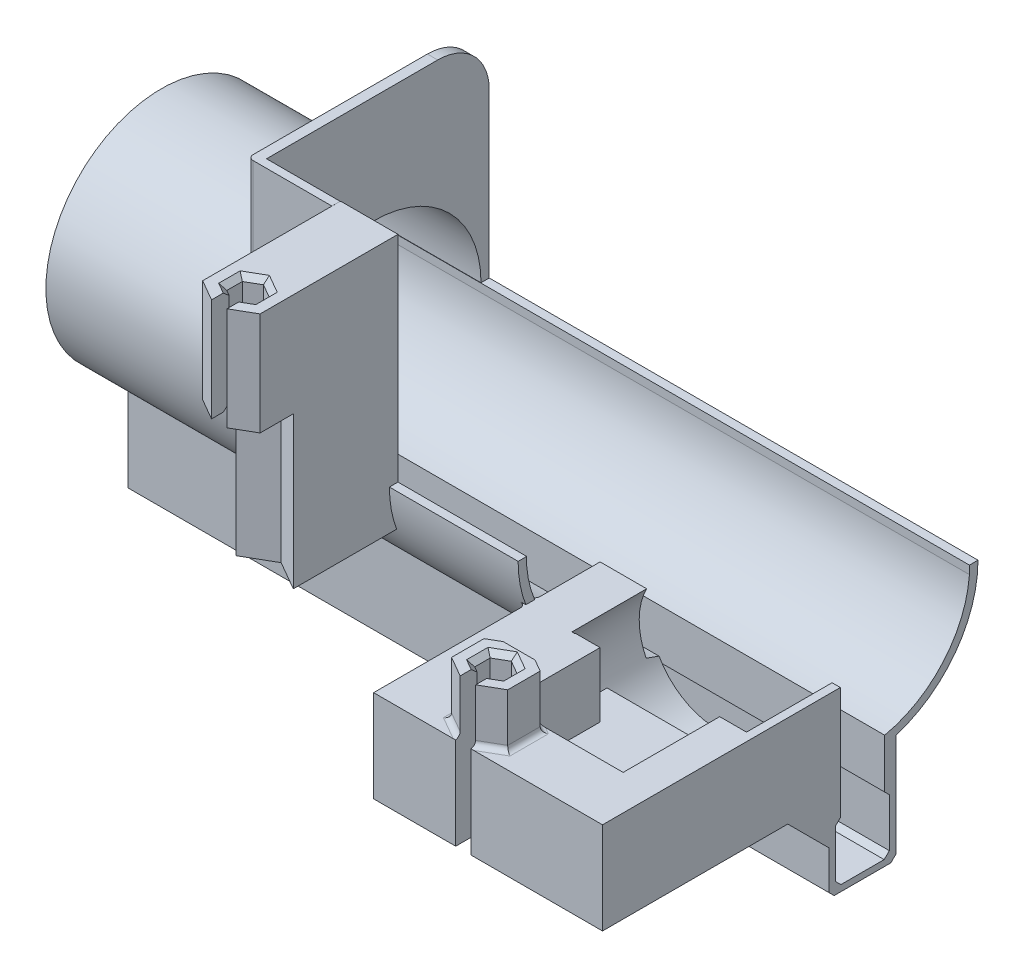
SolidWorks part; units mm, degrees
note: The reader was unsure of these and kept them because the rebuilt part matched: shared geometry of "Sketch6<5>", "Sketch6<6>", "Sketch16<2>", "Sketch18<2>", "Sketch17<3>", "Sketch21<2>", "Sketch18<3>".
ref_plane "Front Plane" through (0, 0, 0) normal (0, 0, 1) x (1, 0, 0)
ref_plane "Top Plane" through (0, 0, 0) normal (0, 1, 0) x (1, 0, 0)
ref_plane "Right Plane" through (0, 0, 0) normal (1, 0, 0) x (0, 0, -1)
sketch "Sketch1" plane through (0, 0, 0) normal (0, 1, 0) x (1, 0, 0)
  line L1 (0, 0) -> (136, 0)
  line L2 (0, 0) -> (0, 13)
  line L3 (0, 13) -> (136, 13)
  line L4 (136, 0) -> (136, 13)
  dimension "D1" = 13
  dimension "D2" = 136
extrude "Boss-Extrude1" add sketch "Sketch1" along normal blind 21
sketch "Sketch4" plane through (136, 0, 0) normal (1, 0, 0) x (0, 0, -1)
  line L0 (1.3, 2.2) -> (2.3, 1.2)
  line L1 (2.3, 12.6) -> (10.7, 12.6)
  line L2 (1.3, 11.6) -> (1.3, 2.2)
  line L3 (2.3, 1.2) -> (10.7, 1.2)
  line L4 (11.7, 11.6) -> (11.7, 2.2)
  line L5 (0, 21) -> (0, 0) construction
  line L6 (0, 0) -> (13, 0) construction
  line L7 (1.3, 2.2) -> (2.3, 1.2)
  line L8 (10.7, 1.2) -> (11.7, 2.2)
  line L10 (1.3, 11.6) -> (2.3, 12.6)
  line L11 (10.7, 12.6) -> (11.7, 11.6)
  dimension "D2" = 1.3
  dimension "D3" = 1.2
  dimension "D4" = 1
  dimension "D5" = 45
  dimension "D6" = 45
  dimension "D7" = 1
  dimension "D8" = 11.4
  dimension "D9" = 45
  dimension "D10" = 45
  dimension "D11" = 1
  dimension "D12" = 1
  dimension "D13" = 8.4
extrude "Cut-Extrude1" cut sketch "Sketch4" against normal blind 135 contours L3 L8 L4 L1 L2 L0
chamfer "Chamfer1" distance 1 angle 45 1 edges at (68, 0, 0)
chamfer "Chamfer2" distance 1 angle 45 1 edges at (68, 0, -13)
sketch "Sketch6" plane through (0, 21, 0) normal (0, 1, 0) x (1, 0, 0)
  line L0 (136, 0) -> (136, 13) construction
  line L1 (1, 10.8) -> (136, 10.8)
  line L2 (1, 10.8) -> (1, 2.2)
  line L3 (1, 2.2) -> (136, 2.2)
  line L4 (136, 10.8) -> (136, 2.2)
  point P4 (136, 6.5)
  dimension "D1" = 135
  dimension "D2" = 8.6
extrude "Cut-Extrude3" cut sketch "Sketch6" against normal blind 9
sketch "Sketch8" plane through (0, 0, 0) normal (-1, 0, 0) x (0, 0, 1)
  line L0 (-13, 21) -> (-13, 1) construction
  line L1 (-10.5, 20) -> (-2.5, 20)
  line L2 (-10.5, 20) -> (-10.5, 12.46)
  line L3 (-10.5, 12.46) -> (-2.5, 12.46)
  line L4 (-2.5, 20) -> (-2.5, 12.46)
  line L5 (-13, 21) -> (0, 21) construction
  line L6 (0, 21) -> (0, 1) construction
  line L8 (-9, 20) -> (-4, 20)
  line L9 (-9, 20) -> (-9, 12.46)
  line L10 (-9, 12.46) -> (-4, 12.46)
  line L11 (-4, 20) -> (-4, 12.46)
  point P14 (-6.5, 20)
  point P15 (-6.5, 20)
  point P16 (-6.5, 12.46)
  point P17 (-6.5, 12.46)
  dimension "D1" = 2.5
  dimension "D2" = 1
  dimension "D3" = 7.54
  dimension "D4" = 2.5
  dimension "D5" = 5
extrude "Cut-Extrude5" cut sketch "Sketch8" against normal blind 1 contours L9 L1 L2 L3 | L1 L11 L3 L4
sketch "Sketch9" plane through (0, 0, 0) normal (-1, 0, 0) x (0, 0, 1)
  line L1 (-13, 20) -> (0, 20) construction
  line L2 (-28.9, 42.4) -> (-27.2384, 42.4)
  line L4 (-27.2384, 42.4) -> (-27.2384, 40.8)
  line L5 (14.2384, 40.8) -> (14.2384, 42.4)
  line L6 (14.2384, 42.4) -> (15.9, 42.4)
  line L7 (-28.9, 42.4) -> (15.9, 42.4) construction
  line L8 (-27.2384, 40.8) -> (14.2384, 40.8) construction
  line L9 (-10.5, 20) -> (-9, 20) construction
  line L12 (-13, 21) -> (-13, 1) construction
  line L13 (0, 21) -> (0, 1) construction
  arc A0 (-28.9, 42.4) -> (15.9, 42.4) centre (-6.5, 42.4) ccw
  arc A1 (-27.2384, 40.8) -> (14.2384, 40.8) centre (-6.5, 42.4) ccw
  point P4 (-6.5, 20)
  dimension "D1" = 44.8
  dimension "D2" = 1.6
extrude "Boss-Extrude3" add sketch "Sketch9" against normal blind 136 separate body
sketch "Sketch11" plane through (0, 0, 0) normal (-1, 0, 0) x (0, 0, 1)
  circle A0 centre (-6.5, 42.4) radius 22.4
  circle A1 centre (-6.5, 42.4) radius 20.8
  dimension "D1" = 44.8
  dimension "D2" = 41.6
extrude "Boss-Extrude6" add sketch "Sketch11" against normal blind 41.2
extrude "Cut-Extrude11" cut sketch "Sketch6<5>" along normal blind 35
sketch "Sketch6<5>" plane through (0, 21, 0) normal (0, 1, 0) x (1, 0, 0) same geometry as "Sketch6"
extrude "Cut-Extrude12" cut sketch "Sketch6<6>" against normal blind 1
sketch "Sketch6<6>" plane through (0, 21, 0) normal (0, 1, 0) x (1, 0, 0) same geometry as "Sketch6"
sketch "Sketch13" plane through (0, 0, 0) normal (0, 0, 1) x (1, 0, 0)
  line L1 (136, 20.9638) -> (89, 20.9638)
  line L2 (136, 20.9638) -> (136, 42.9638)
  line L3 (136, 42.9638) -> (89, 42.9638)
  line L4 (89, 20.9638) -> (89, 42.9638)
  dimension "D1" = 47
  dimension "D2" = 22
extrude "Cut-Extrude13" cut sketch "Sketch13" along normal blind 32
ref_plane "Plane1" through (136, 22.0493, -2.2) normal (1, 0, 0) x (0, 0, -1)
ref_plane "Plane2" through (0, 22.7, 0) normal (0, 1, 0) x (1, 0, 0)
sketch "Sketch16" plane through (0, 22.7, 0) normal (0, 1, 0) x (1, 0, 0)
  line L0 (136, 0) -> (89, 0) construction
  line L1 (109.0218, -40.64) -> (111.6198, -39.14)
  line L2 (111.6198, -39.14) -> (111.6198, -36.14)
  line L3 (111.6198, -36.14) -> (109.0218, -34.64)
  line L4 (109.0218, -34.64) -> (106.4237, -36.14)
  line L5 (106.4237, -36.14) -> (106.4237, -39.14)
  line L6 (106.4237, -39.14) -> (109.0218, -40.64)
  line L8 (109.0218, -31.35) -> (103.5745, -34.495)
  line L9 (103.5745, -34.495) -> (103.5745, -40.785)
  line L10 (103.5745, -40.785) -> (109.0218, -43.93)
  line L11 (109.0218, -43.93) -> (114.4691, -40.785)
  line L12 (114.4691, -40.785) -> (114.4691, -34.495)
  line L13 (114.4691, -34.495) -> (109.0218, -31.35)
  circle A0 centre (109.0218, -37.64) radius 2.5981 construction
  circle A1 centre (109.0218, -37.64) radius 5.4473 construction
  dimension "D1" = 6
  dimension "D2" = 34.64
  dimension "D3" = 40.01
  dimension "D4" = 12.58
extrude "Boss-Extrude7" add sketch "Sketch16" along normal blind 22 separate body
extrude "Boss-Extrude8" add sketch "Sketch16<2>" against normal blind 4.79
sketch "Sketch16<2>" plane through (0, 22.7, 0) normal (0, 1, 0) x (1, 0, 0) same geometry as "Sketch16"
sketch "Sketch17" plane through (0, 17.91, 0) normal (0, -1, 0) x (1, 0, 0)
  line L1 (94.0218, 43.93) -> (136, 43.93)
  line L3 (94.0218, 0) -> (136, 0)
  line L4 (136, 43.93) -> (136, 0)
  line L5 (0, 0) -> (136, 0) construction
  line L6 (94.0218, 0) -> (91.6018, 0)
  line L7 (91.6018, 0) -> (91.6018, 43.93)
  line L8 (91.6018, 43.93) -> (94.0218, 43.93)
  dimension "D1" = 2.42
  dimension "D2" = 15
extrude "Boss-Extrude10" add sketch "Sketch17" against normal blind 16.45
sketch "Sketch18" plane through (0, 0, 0) normal (0, 0, 1) x (1, 0, 0)
  circle A0 centre (112.185, 28.4) radius 13
  circle A1 centre (112.185, 28.4) radius 9.75 construction
  dimension "D1" = 26
extrude "Cut-Extrude14" cut sketch "Sketch18" against normal blind 8
extrude "Cut-Extrude15" cut sketch "Sketch18<2>" along normal blind 8
sketch "Sketch18<2>" plane through (0, 0, 0) normal (0, 0, 1) x (1, 0, 0) same geometry as "Sketch18"
sketch "Sketch21" plane through (0, 34.36, 0) normal (0, 1, 0) x (1, 0, 0)
  line L0 (136, -43.93) -> (109.0218, -43.93) construction
  line L1 (106, -8) -> (129.2, -8)
  line L2 (106, -8) -> (106, -33.13)
  line L3 (106, -33.13) -> (129.2, -33.13)
  line L4 (129.2, -8) -> (129.2, -33.13)
  line L5 (136, 0) -> (136, -43.93) construction
  line L6 (123.7383, -8) -> (100.6317, -8) construction
  dimension "D1" = 10.8
  dimension "D2" = 6.8
  dimension "D3" = 23.2
extrude "Cut-Extrude16" cut sketch "Sketch21" against normal blind 12.5
extrude "Boss-Extrude11" add sketch "Sketch17<3>" along normal blind 1.39
sketch "Sketch17<3>" plane through (0, 17.91, 0) normal (0, -1, 0) x (1, 0, 0) same geometry as "Sketch17"
extrude "Cut-Extrude18" cut sketch "Sketch21<2>" along normal blind 33.8
sketch "Sketch21<2>" plane through (0, 34.36, 0) normal (0, 1, 0) x (1, 0, 0) same geometry as "Sketch21"
sketch "Sketch23" plane through (0, 34.36, 0) normal (0, 1, 0) x (1, 0, 0)
  line L1 (101.2, -8) -> (123.7383, -8)
  line L2 (101.2, -8) -> (101.2, -14.4)
  line L3 (101.2, -14.4) -> (134.4, -14.4)
  line L4 (134.4, -8) -> (134.4, -14.4)
  line L6 (129.2, -33.13) -> (129.2, -8) construction
  line L7 (104.5065, -8) -> (99.185, -8) construction
  line L10 (134.4, -8) -> (134.4, 0.5)
  line L11 (134.4, 0.5) -> (123.7383, 0.5)
  line L12 (123.7383, -8) -> (123.7383, 0.5)
  line L13 (129.2, -33.13) -> (129.2, -8) construction
  line L14 (123.7383, -8) -> (123.7383, 0) construction
  dimension "D1" = 33.2
  dimension "D2" = 5.2
  dimension "D3" = 6.4
  dimension "D4" = 14.9
extrude "Cut-Extrude20" cut sketch "Sketch23" against normal blind 12.5
sketch "Sketch24" plane through (0, 0, 14.4) normal (0, 0, -1) x (-1, 0, 0)
  line L1 (-134.4, 21.86) -> (-134.4, 34.36) construction
  line L2 (-101.2, 21.86) -> (-101.2, 34.36) construction
  line L3 (-101.2, 34.36) -> (-106, 34.36) construction
  line L4 (-129.2, 34.36) -> (-134.4, 34.36) construction
  circle A0 centre (-131.31, 28.41) radius 1.2
  circle A1 centre (-103.81, 28.41) radius 1.2
  dimension "D2" = 3.09
  dimension "D3" = 2.4
  dimension "D4" = 2.4
  dimension "D1" = 5.95
  dimension "D5" = 2.61
  dimension "D6" = 5.95
extrude "Cut-Extrude21" cut sketch "Sketch24" against normal blind 12
sketch "Sketch25" plane through (0, 16.52, 0) normal (0, -1, 0) x (1, 0, 0)
  line L1 (109.0218, 34.64) -> (111.6198, 36.14)
  line L2 (111.6198, 36.14) -> (111.6198, 39.14)
  line L3 (111.6198, 39.14) -> (109.0218, 40.64)
  line L4 (109.0218, 40.64) -> (106.4237, 39.14)
  line L5 (106.4237, 39.14) -> (106.4237, 36.14)
  line L6 (106.4237, 36.14) -> (109.0218, 34.64)
  circle A0 centre (109.0218, 37.64) radius 2.5981 construction
extrude "Cut-Extrude22" cut sketch "Sketch25" against normal blind 30
extrude "Cut-Extrude23" cut sketch "Sketch18<3>" along normal blind 8
sketch "Sketch18<3>" plane through (0, 0, 0) normal (0, 0, 1) x (1, 0, 0) same geometry as "Sketch18"
chamfer "Chamfer3" distance 8 angle 45 1 edges at (126.7319, 16.52, 0)
sketch "Sketch26" plane through (0, 21.86, 0) normal (0, 1, 0) x (1, 0, 0)
  line L1 (136, 0) -> (123.5282, 0)
  line L2 (136, 0) -> (136, 2.2)
  line L3 (136, 2.2) -> (123.5282, 2.2)
  line L4 (123.5282, 0) -> (123.5282, 2.2)
extrude "Cut-Extrude24" cut sketch "Sketch26" along normal blind 8
sketch "Sketch27" plane through (0, 0, 8) normal (0, 0, 1) x (1, 0, 0)
  line L0 (123.7383, 21.86) -> (123.7383, 22.44)
  line L1 (123.7383, 21.86) -> (123.7383, 22.44) construction
  line L2 (123.7383, 22.44) -> (123.4201, 21.86)
  line L3 (123.4201, 21.86) -> (123.7383, 21.86)
  arc A0 (123.4201, 21.86) -> (123.7383, 22.44) centre (112.185, 28.4) ccw construction
extrude "Cut-Extrude25" cut sketch "Sketch27" against normal blind 11
sketch "Sketch28" plane through (0, 21.86, 0) normal (0, 1, 0) x (1, 0, 0)
  line L0 (136, 2.2) -> (123.4201, 2.2) construction
  line L1 (136, 0) -> (134.4, 0)
  line L2 (136, 0) -> (136, 2.2)
  line L3 (136, 2.2) -> (134.4, 2.2)
  line L4 (134.4, 0) -> (134.4, 2.2)
  line L5 (134.4, -14.4) -> (134.4, 0) construction
extrude "Boss-Extrude14" add sketch "Sketch28" along normal blind 12.5
sketch "Sketch29" plane through (0, 0, 8) normal (0, 0, -1) x (-1, 0, 0)
  line L0 (-101.2, 21.86) -> (-101.2, 34.36)
  line L1 (-101.2, 34.36) -> (-100.6317, 34.36)
  line L2 (-109.0218, 34.36) -> (-91.6018, 34.36) construction
  line L3 (-100.6317, 34.36) -> (-101.2, 34.36) construction
  line L4 (-101.2, 21.86) -> (-100.5299, 22.6417)
  line L5 (-101.2, 21.86) -> (-100.9499, 21.86)
  arc A0 (-100.9499, 21.86) -> (-100.6317, 34.36) centre (-112.185, 28.4) ccw
  line M1 (-100.6317, 34.36) -> (-101.2, 34.36)
  line M2 (-101.2, 34.36) -> (-101.2, 21.86)
  arc M6 (-106.9062, 16.52) -> (-100.6317, 34.36) centre (-112.185, 28.4) ccw
  dimension "D1" = 26
extrude "Cut-Extrude26" cut sketch "Sketch29" against normal blind 6.5 contours L4 M2 M6 M1 | L4 L5 M6
fillet "Fillet2" radius 1 3 edges at (111.7454, 34.36, 42.3575) (113.2869, 34.36, 33.8125) (114.4691, 34.36, 37.64)
fillet "Fillet3" radius 1 3 edges at (104.7872, 34.36, 33.7948) (103.5745, 34.36, 37.64) (106.2981, 34.36, 42.3575)
sketch "Sketch30" plane through (89, 0, 0) normal (1, 0, 0) x (0, 0, -1)
  line L0 (-14.2384, 42.4) -> (-15.9, 42.4)
  line L1 (27.2384, 42.4) -> (28.9, 42.4)
  line L2 (2.2, 20.4166) -> (2.2, 22.0493)
  line L3 (2.2, 12.5) -> (2.2, 22.0493) construction
  arc A0 (-14.2384, 42.4) -> (27.2384, 42.4) centre (6.5, 42.4) ccw
  arc A1 (-15.9, 42.4) -> (28.9, 42.4) centre (6.5, 42.4) ccw
  dimension "D1" = 44.8
extrude "Boss-Extrude15" add sketch "Sketch30" along normal up to surface (2.6018 mm away) up to face at (91.6018, 22.1536, 15.9767)
fillet "Fillet5" radius 1 1 edges at (91.6018, 27.1225, 7.6151)
fillet "Fillet6" radius 1 1 edges at (91.6018, 25.9956, 8.753)
ref_plane "Plane3" through (0, 64.02, 0) normal (0, 1, 0) x (1, 0, 0)
sketch "Sketch31" plane through (0, 64.02, 0) normal (0, 1, 0) x (1, 0, 0)
  line L0 (91.6018, -15.9) -> (41.2, -15.9) construction
  line L1 (61.0618, -40.76) -> (63.6598, -39.26)
  line L2 (63.6598, -39.26) -> (63.6598, -36.26)
  line L3 (63.6598, -36.26) -> (61.0618, -34.76)
  line L4 (61.0618, -34.76) -> (58.4637, -36.26)
  line L5 (58.4637, -36.26) -> (58.4637, -39.26)
  line L6 (58.4637, -39.26) -> (61.0618, -40.76)
  line L7 (103.5745, -34.495) -> (103.5745, -40.785) construction
  line L9 (61.0618, -31.325) -> (55.4889, -34.5425)
  line L10 (55.4889, -34.5425) -> (55.4889, -40.9775)
  line L11 (55.4889, -40.9775) -> (61.0618, -44.195)
  line L12 (61.0618, -44.195) -> (66.6346, -40.9775)
  line L13 (66.6346, -40.9775) -> (66.6346, -34.5425)
  line L14 (66.6346, -34.5425) -> (61.0618, -31.325)
  line L15 (91.6018, -15.9) -> (91.6018, -14.2384) construction
  circle A0 centre (61.0618, -37.76) radius 2.5981 construction
  circle A1 centre (61.0618, -37.76) radius 5.5729 construction
  dimension "D1" = 6
  dimension "D2" = 12.87
  dimension "D3" = 18.86
  dimension "D4" = 30.54
extrude "Boss-Extrude16" add sketch "Sketch31" along normal blind 20 separate body
ref_plane "Plane5" through (0, 0, 14.2384) normal (0, 0, -1) x (-1, 0, 0)
sketch "Sketch32" plane through (0, 84.02, 0) normal (0, 1, 0) x (1, 0, 0)
  line L0 (55.4889, -34.5425) -> (55.4889, -14.2384)
  line L3 (66.6346, -34.5425) -> (66.6346, -14.2384)
  line L5 (66.6346, -14.2384) -> (55.4889, -14.2384)
  line L6 (55.4889, -34.5425) -> (61.0618, -31.325)
  line L7 (61.0618, -31.325) -> (66.6346, -34.5425)
  line L8 (91.6018, -14.2384) -> (0, -14.2384) construction
  line M1 (66.6346, -34.5425) -> (61.0618, -31.325)
  line M2 (61.0618, -31.325) -> (55.4889, -34.5425)
extrude "Boss-Extrude17" add sketch "Sketch32" against normal blind 49.4 contours L3 L5 L0 M2 M1
sketch "Sketch36" plane through (0, 0, 14.2384) normal (0, 0, -1) x (-1, 0, 0)
  line L1 (-66.6318, 42.4) -> (-55.4818, 42.4)
  line L2 (-66.6318, 42.4) -> (-66.6318, 34.62)
  line L3 (-66.6318, 34.62) -> (-55.4818, 34.62)
  line L4 (-55.4818, 42.4) -> (-55.4818, 34.62)
  line L5 (-91.6018, 40.8) -> (-91.6018, 34.36) construction
  line L6 (-107.0218, 34.36) -> (-91.6018, 34.36) construction
  dimension "D1" = 24.97
  dimension "D2" = 11.15
  dimension "D3" = 7.78
  dimension "D4" = 0.26
extrude "Cut-Extrude27" cut sketch "Sketch36" against normal blind 20
sketch "Sketch37" plane through (41.2, 0, 0) normal (1, 0, 0) x (0, 0, -1)
  line L2 (-15.9, 42.4) -> (-15.9, 84.02)
  line L3 (-15.9, 84.02) -> (28.9, 84.02)
  line L4 (28.9, 42.4) -> (28.9, 84.02)
  arc A0 (28.9, 42.4) -> (-15.9, 42.4) centre (6.5, 42.4) ccw
  dimension "D3" = 44.8
  dimension "D1" = 41.62
extrude "Boss-Extrude18" add sketch "Sketch37" against normal blind 2
fillet "Fillet10" radius 10 1 edges at (40.2, 84.02, -28.9)
sketch "Sketch39" plane through (0, 42.4, 0) normal (0, 1, 0) x (1, 0, 0)
  line L1 (41.2, -14.3) -> (55.4818, -14.3)
  line L2 (41.2, -14.3) -> (41.2, -15.9)
  line L3 (41.2, -15.9) -> (55.4818, -15.9)
  line L4 (55.4818, -14.3) -> (55.4818, -15.9)
extrude "Boss-Extrude19" add sketch "Sketch39" along normal blind 41.62
fillet "Fillet11" radius 1 1 edges at (39.2, 63.21, 15.9)
sketch "Sketch40" plane through (0, 84.02, 0) normal (0, 1, 0) x (1, 0, 0)
  line L0 (61.0618, -40.76) -> (61.0618, -44.195) construction
  line L1 (59.5618, -39.894) -> (59.5618, -43.329)
  line L2 (58.4637, -39.26) -> (61.0618, -40.76) construction
  line L3 (55.4889, -40.9775) -> (61.0618, -44.195) construction
  line L4 (62.5618, -39.894) -> (62.5618, -43.329)
  line L5 (61.0618, -40.76) -> (63.6598, -39.26) construction
  line L6 (61.0618, -44.195) -> (66.6346, -40.9775) construction
  line L7 (61.0618, -44.195) -> (59.5618, -43.329)
  line L8 (61.0618, -44.195) -> (62.5618, -43.329)
  line L9 (59.5618, -39.894) -> (61.0618, -40.76)
  line L10 (61.0618, -40.76) -> (62.5618, -39.894)
  dimension "D1" = 1.5
  dimension "D2" = 1.5
extrude "Cut-Extrude28" cut sketch "Sketch40" against normal blind 25
sketch "Sketch41" plane through (0, 44.7, 0) normal (0, 1, 0) x (1, 0, 0)
  line L0 (109.0218, -40.64) -> (109.0218, -43.93) construction
  line L1 (107.5218, -39.774) -> (107.5218, -43.064)
  line L2 (106.4237, -39.14) -> (109.0218, -40.64) construction
  line L3 (103.5745, -40.785) -> (109.0218, -43.93) construction
  line L4 (110.5218, -39.774) -> (110.5218, -43.064)
  line L5 (109.0218, -40.64) -> (111.6198, -39.14) construction
  line L6 (109.0218, -43.93) -> (114.4691, -40.785) construction
  line L7 (107.5218, -39.774) -> (109.0218, -40.64)
  line L8 (109.0218, -40.64) -> (110.5218, -39.774)
  line L11 (107.5218, -43.064) -> (107.5218, -44.7038)
  line L12 (107.5218, -44.7038) -> (110.5218, -44.7038)
  line L13 (110.5218, -44.7038) -> (110.5218, -43.064)
  dimension "D1" = 1.5
  dimension "D2" = 1.5
extrude "Cut-Extrude31" cut sketch "Sketch41" against normal blind 30
chamfer "Chamfer4" distance 1 angle 45 12 edges at (59.0127, 64.02, 39.577) (58.4637, 64.02, 37.76) (63.1108, 64.02, 39.577) (63.6598, 64.02, 37.76) (62.3608, 64.02, 35.51) (59.7627, 64.02, 35.51) (63.1108, 84.02, 39.577) (63.6598, 84.02, 37.76) (59.0127, 84.02, 39.577) (58.4637, 84.02, 37.76) (62.3608, 84.02, 35.51) (59.7627, 84.02, 35.51)
chamfer "Chamfer5" distance 1 angle 45 12 edges at (106.9727, 16.52, 39.457) (106.4237, 16.52, 37.64) (107.7227, 16.52, 35.39) (110.3208, 16.52, 35.39) (111.6198, 16.52, 37.64) (111.0708, 16.52, 39.457) (106.9727, 44.7, 39.457) (111.0708, 44.7, 39.457) (111.6198, 44.7, 37.64) (106.4237, 44.7, 37.64) (110.3208, 44.7, 35.39) (107.7227, 44.7, 35.39)
